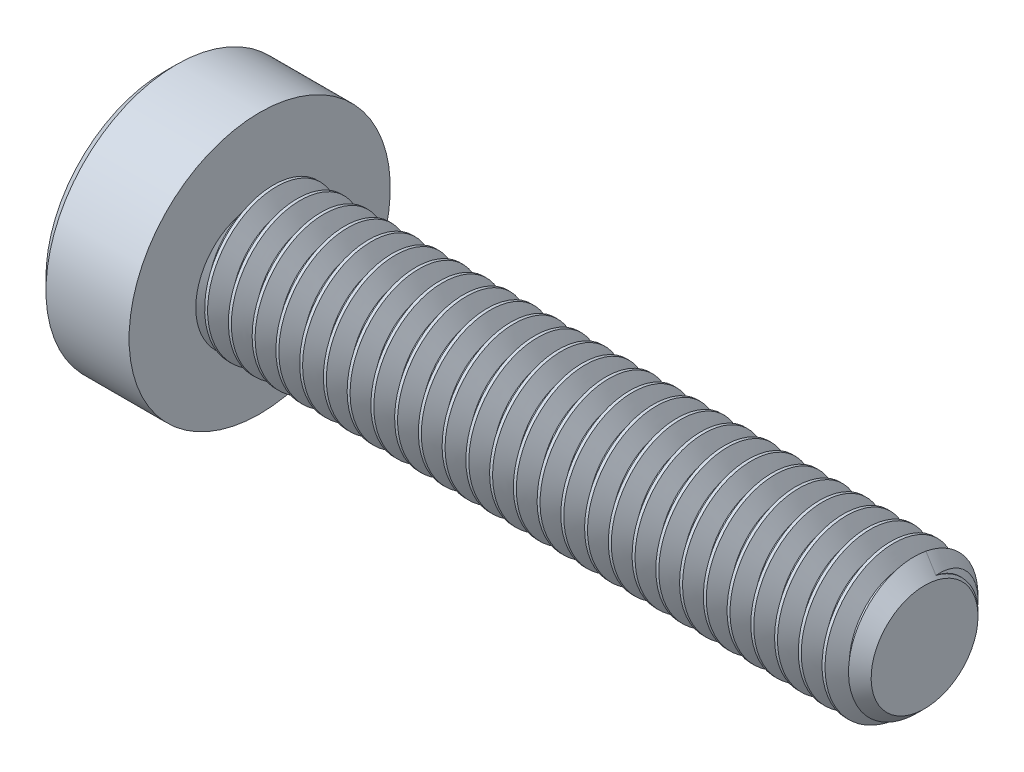
SolidWorks part; units mm, degrees
ref_plane "Front Plane" through (0, 0, 0) normal (0, 0, 1) x (1, 0, 0)
ref_plane "Top Plane" through (0, 0, 0) normal (0, 1, 0) x (1, 0, 0)
ref_plane "Right Plane" through (0, 0, 0) normal (1, 0, 0) x (0, 0, -1)
sketch "Sketch1" plane through (0, 0, 0) normal (0, 0, 1) x (1, 0, 0)
  line L0 (7, 0) -> (-7, 0) construction
  line L1 (7, 1.5) -> (7, -1.5) construction
  line L2 (-7, 2.75) -> (-7, -2.75) construction
  line L3 (-7, 2.75) -> (-8.75, 2.75) construction
  line L4 (-8.75, 2.75) -> (-9, 2.5) construction
  line L5 (-9, 2.5) -> (-9, -2.5) construction
  line L6 (-9, -2.5) -> (-8.75, -2.75) construction
  line L7 (-8.75, -2.75) -> (-7, -2.75) construction
  point P7 (-7.38, 0)
  point P12 (5, -1.5)
  dimension "D1" = 45
  dimension "Dec." = 3
  dimension "Length" = 14
  dimension "Head Dia" = 5.5
  dimension "Head Height" = 2
  dimension "Hex Depth" = 1.62
  dimension "Chamfer" = 0.25
  dimension "D2" = 2
ref_plane "Plane1" through (7, 0, 0) normal (1, 0, 0) x (0, 0, -1)
ref_plane "Plane2" through (-9, 0, 0) normal (1, 0, 0) x (0, 0, -1)
sketch "Sketch2" plane through (7, 0, 0) normal (1, 0, 0) x (0, 0, -1)
  circle A0 centre (0, 0) radius 1.5
extrude "Boss-Extrude1" add sketch "Sketch2" against normal up to vertex (14 mm away) up to point (-7, 0, 0)
sketch "Sketch3" plane through (7, 0, 0) normal (1, 0, 0) x (0, 0, -1)
  circle A0 centre (0, 0) radius 1.5 construction
  circle A1 centre (0, 0) radius 1.5
curve "Helix/Spiral1" pitch 0.5 height 14.5 radius 1.5 centre (7, 0, 0) axis (-1, 0, 0) start towards (0, 1, 0) parameters "Pitch"=0.5
chamfer "Chamfer1" distance 0.375 angle 45 1 edges at (7, 0, -1.5)
sketch "Sketch5" plane through (0, 0, 0) normal (0, 0, 1) x (1, 0, 0)
  line L0 (6.7813, 1.5) -> (7.2188, 1.5)
  line L1 (7.2188, 1.5) -> (7.0313, 1.1752)
  line L2 (7.0313, 1.1752) -> (6.9688, 1.1752)
  line L3 (6.9688, 1.1752) -> (6.7813, 1.5)
  line L4 (7, 1.1752) -> (7, 1.5) construction
  line L5 (6.875, 1.3376) -> (7.125, 1.3376) construction
  dimension "D1" = 60
  dimension "D2" = 0.25
  dimension "D3" = 0.0625
sweep "Cut-Sweep1" cut profiles "Sketch5" path "Helix/Spiral1" align with end faces yes
sketch "Sketch4" plane through (-9, 0, 0) normal (1, 0, 0) x (0, 0, -1)
  line L0 (-2.75, 0.7937) -> (2.75, 0.7937) construction
  line L1 (0, 1.1547) -> (-1, 0.5774)
  line L2 (-1, 0.5774) -> (-1, -0.5774)
  line L3 (-1, -0.5774) -> (0, -1.1547)
  line L4 (0, -1.1547) -> (1, -0.5774)
  line L5 (1, -0.5774) -> (1, 0.5774)
  line L6 (1, 0.5774) -> (0, 1.1547)
  line L7 (0, 0) -> (0, 0.7937) construction
  circle A0 centre (0, 0) radius 1 construction
  dimension "Hex Size" = 2
  dimension "D1" = 5.5
  dimension "D2" = 0.7937
sketch "Sketch6" plane through (0, 0, 0) normal (0, 0, 1) x (1, 0, 0)
  line L0 (-8.75, 2.75) -> (-9, 2.5) construction
  line L1 (-7, 2.75) -> (-8.75, 2.75) construction
  line L2 (-7, 2.75) -> (-7, -2.75) construction
  line L3 (-9, 2.5) -> (-9, -2.5) construction
  line L4 (-8.75, 2.75) -> (-9, 2.5)
  line L5 (-7, 2.75) -> (-8.75, 2.75)
  line L6 (-7, 2.75) -> (-7, 0)
  line L7 (-9, 2.5) -> (-9, 0)
  line L8 (-7, 0) -> (-9, 0) construction
  line L9 (-7, 0) -> (-9, 0)
revolve "Revolve1" add sketch "Sketch6" angle 360 about L8
extrude "Cut-Extrude1" cut sketch "Sketch4" along normal up to vertex (1.62 mm away) up to point (-7.38, 0, 0)
sketch "Sketch8" plane through (-9, 0, 0) normal (-1, 0, 0) x (0, 0, 1)
  circle A1 centre (0, 0) radius 1.1547
extrude "Cut-Extrude2" cut sketch "Sketch8" against normal through all draft 45
equation "\"D3@Helix/Spiral1\" = \"Length@Sketch1\"+\"Pitch@Helix/Spiral1\""
equation "\"D3@Sketch5\" = \"Pitch@Helix/Spiral1\"*.125"
equation "\"D2@Sketch5\" = \"Pitch@Helix/Spiral1\"*.50"
equation "\"D1@Chamfer1\" = \"Pitch@Helix/Spiral1\"*.75"
equation "\"D2@Sketch1\" = \"Pitch@Helix/Spiral1\"*4"
equation "\"D1@Sketch4\" = \"Head Dia@Sketch1\""
equation "\"Chamfer@Sketch1\" = \"Head Height@Sketch1\"/8"
